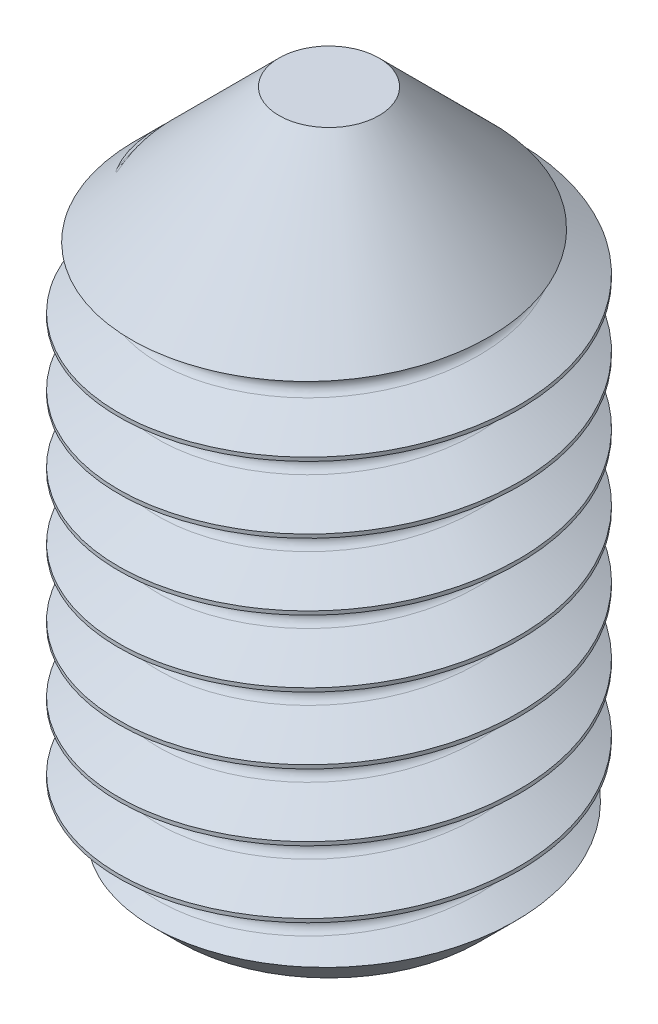
SolidWorks part; units mm, degrees
ref_plane "Front Plane" through (0, 0, 0) normal (0, 0, 1) x (1, 0, 0)
ref_plane "Top Plane" through (0, 0, 0) normal (0, 1, 0) x (1, 0, 0)
ref_plane "Right Plane" through (0, 0, 0) normal (1, 0, 0) x (0, 0, -1)
sketch "Sketch1" plane through (0, 0, 0) normal (0, 1, 0) x (1, 0, 0)
  circle A0 centre (0, 0) radius 1.5
  dimension "D1" = 3
extrude "Boss-Extrude1" add sketch "Sketch1" along normal mid plane 5
sketch "Sketch2" plane through (0, 0, 0) normal (0, 0, 1) x (1, 0, 0)
  line L0 (0.375, 2.5) -> (2.4324, 0.4426)
  line L1 (2.4324, 0.4426) -> (2.4324, -1.1926)
  line L2 (2.4324, -1.1926) -> (1.125, -2.5)
  line L3 (1.125, -2.5) -> (1.125, -3.9071)
  line L4 (1.125, -3.9071) -> (2.7606, -3.9071)
  line L5 (2.7606, -3.9071) -> (2.7606, 3.3192)
  line L6 (2.7606, 3.3192) -> (0.375, 3.3192)
  line L7 (0.375, 3.3192) -> (0.375, 2.5)
  line L8 (0, 0) -> (0, -3.1523) construction
  line L9 (1.5, 2.5) -> (-1.5, 2.5) construction
  line L10 (-1.5, -2.5) -> (1.5, -2.5) construction
  dimension "D1" = 0.75
  dimension "D2" = 2.25
  dimension "D3" = 135
  dimension "D4" = 135
revolve "Cut-Revolve1" cut sketch "Sketch2" angle 360 about L8
sketch "Sketch3" plane through (0, -2.5, 0) normal (0, -1, 0) x (1, 0, 0)
  line L1 (0.775, -0.4474) -> (0.775, 0.4474)
  line L2 (0.775, 0.4474) -> (0, 0.8949)
  line L3 (0, 0.8949) -> (-0.775, 0.4474)
  line L4 (-0.775, 0.4474) -> (-0.775, -0.4474)
  line L5 (-0.775, -0.4474) -> (0, -0.8949)
  line L6 (0, -0.8949) -> (0.775, -0.4474)
  circle A0 centre (0, 0) radius 0.775 construction
  dimension "D1" = 1.55
extrude "Cut-Extrude1" cut sketch "Sketch3" against normal blind 1.5
sketch "Sketch4" plane through (0, -2.5, 0) normal (0, -1, 0) x (1, 0, 0)
  circle A0 centre (0, 0) radius 1.5 construction
  circle A1 centre (0, 0) radius 1.5
curve "Helix/Spiral1" pitch 0.5 height 5.25 turns 10.5
sketch "Sketch5" plane through (0, 0, 0) normal (0, 0, 1) x (1, 0, 0)
  line L1 (1.523, -2.2963) -> (1.1991, -2.4833)
  line L2 (1.1991, -2.6083) -> (1.523, -2.7953)
  line L3 (1.523, -2.7953) -> (1.523, -2.2963)
  circle A0 centre (1.379, -2.5458) radius 0.144 construction
  arc A1 (1.1991, -2.4833) -> (1.1991, -2.6083) centre (1.2352, -2.5458) ccw
  point P7 (1.3497, -2.4281)
  point P8 (1.3631, -2.5523)
  point P9 (0, 0)
  point P10 (1.379, -2.5458)
  dimension "D2" = 0.0722
  dimension "D1" = 0.499
sweep "Cut-Sweep1" cut profiles "Sketch5" path "Helix/Spiral1" align with end faces yes
sketch "Sketch6" plane through (0, -2.5, 0) normal (0, -1, 0) x (1, 0, 0)
  circle A0 centre (0, 0) radius 0.8949
extrude "Cut-Extrude2" cut sketch "Sketch6" against normal blind 1 draft 75
